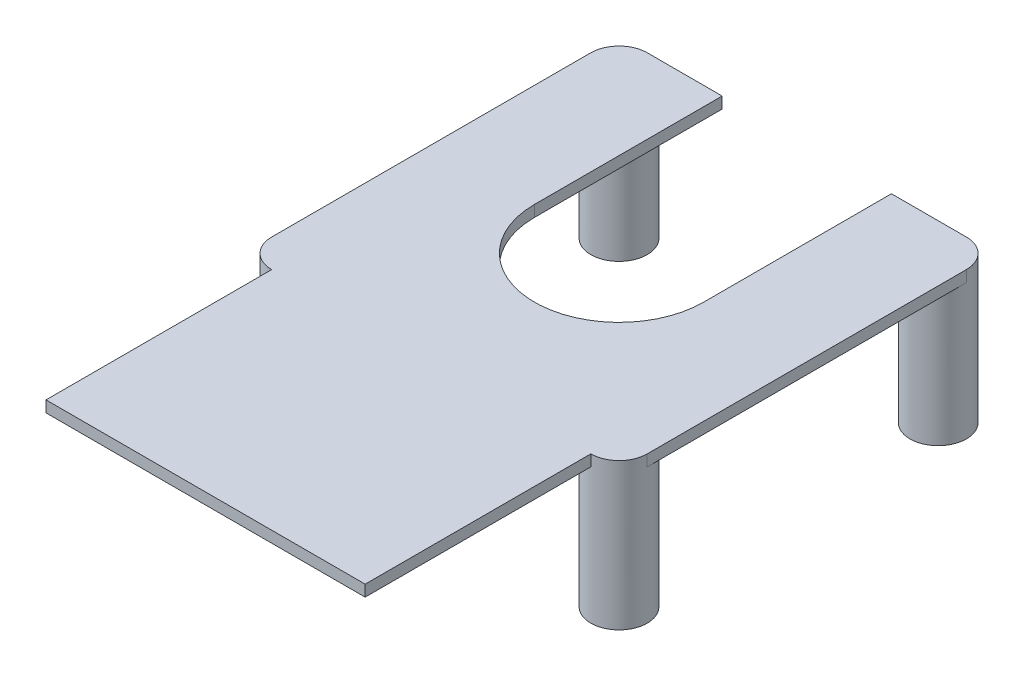
SolidWorks part; units mm, degrees
ref_plane "Front Plane" through (0, 0, 0) normal (0, 0, 1) x (1, 0, 0)
ref_plane "Top Plane" through (0, 0, 0) normal (0, 1, 0) x (1, 0, 0)
ref_plane "Right Plane" through (0, 0, 0) normal (1, 0, 0) x (0, 0, -1)
sketch "Sketch1" plane through (0, 0, 0) normal (0, 1, 0) x (1, 0, 0)
  line L0 (-15, 33.285) -> (-15, 66.57)
  line L5 (15, 33.285) -> (15, 66.57)
  line L6 (-33.285, 5) -> (-33.285, 61.57)
  line L7 (-28.285, 66.57) -> (28.285, 66.57)
  line L8 (28.285, 0) -> (-28.285, 0)
  line L9 (33.285, 61.57) -> (33.285, 5)
  line L11 (28.285, 0) -> (-28.285, 0)
  line L12 (28.285, 0) -> (28.285, -40)
  line L13 (28.285, -40) -> (-28.285, -40)
  line L14 (-28.285, 0) -> (-28.285, -40)
  circle A0 centre (-28.285, 5) radius 5
  circle A1 centre (28.285, 5) radius 5
  circle A2 centre (-28.285, 61.57) radius 5
  circle A3 centre (28.285, 61.57) radius 5
  arc A4 (-15, 33.285) -> (15, 33.285) centre (0, 33.285) ccw
  point P4 (0, 0)
  point P13 (-33.285, 33.285)
  dimension "D2" = 10
  dimension "D3" = 30
  dimension "D1" = 56.57
  dimension "D4" = 56.57
  dimension "D5" = 40
extrude "Boss-Extrude1" add sketch "Sketch1" against normal blind 24 contours A0 | A2 | A3 | A1 region at (-28.285, 0, -61.57) region at (28.285, 0, -61.57) region at (-28.285, 0, -5)
extrude "Boss-Extrude3" add sketch "Sketch1<5>" along normal blind 2 contours A4 L0 L7 A2 L6 A0 L8 A1 L9 A3 L5 | L8 L14 L13 L12 | A2 | A3 | A1 | A0 region at (0, 0, -17.3436) region at (-28.285, 0, -61.57) region at (28.285, 0, -61.57) region at (-28.285, 0, -5) region at (0, 0, 20) region at (28.285, 0, -5)
sketch "Sketch1<5>" plane through (0, 0, 0) normal (0, 1, 0) x (1, 0, 0) same geometry as "Sketch1"
